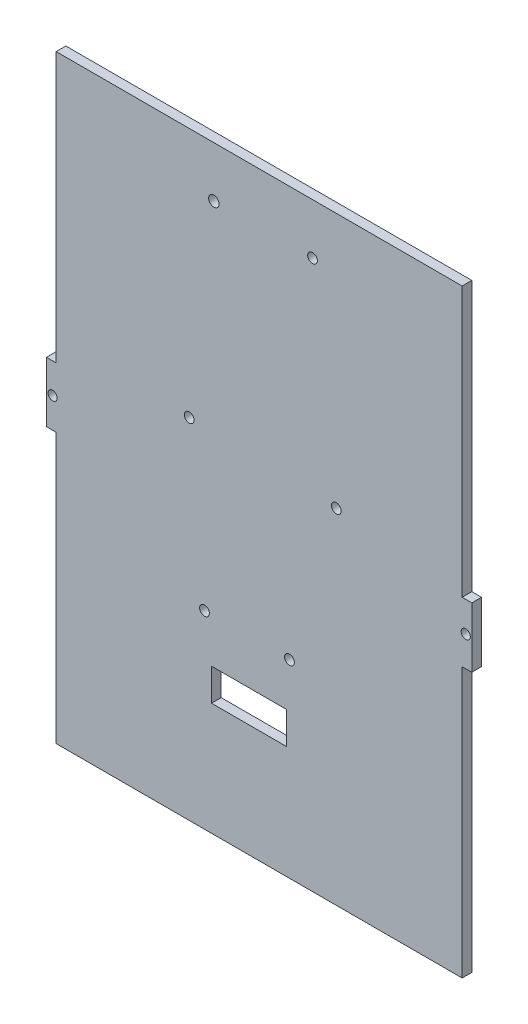
SolidWorks part; units mm, degrees
ref_plane "Front Plane" through (0, 0, 0) normal (0, 0, 1) x (1, 0, 0)
ref_plane "Top Plane" through (0, 0, 0) normal (0, 1, 0) x (1, 0, 0)
ref_plane "Right Plane" through (0, 0, 0) normal (1, 0, 0) x (0, 0, -1)
sketch "Sketch1" plane through (0, 0, 0) normal (0, 0, 1) x (1, 0, 0)
  line L1 (-69.85, 101.6) -> (69.85, 101.6)
  line L2 (-69.85, 101.6) -> (-69.85, -101.6)
  line L3 (-69.85, -101.6) -> (69.85, -101.6)
  line L4 (69.85, 101.6) -> (69.85, -101.6)
  line L5 (-69.85, 101.6) -> (69.85, -101.6) construction
  line L6 (-69.85, -101.6) -> (69.85, 101.6) construction
  point P0 (0, 0)
  dimension "D1" = 203.2
  dimension "D2" = 139.7
extrude "Boss-Extrude1" add sketch "Sketch1" along normal blind 3.18
sketch "Sketch2" plane through (0, 0, 3.18) normal (0, 0, 1) x (1, 0, 0)
  line L0 (0, 0) -> (69.85, 0) construction
  line L1 (-10, 101.6) -> (10, 101.6)
  line L2 (-10, 101.6) -> (-10, 98.42)
  line L3 (-10, 98.42) -> (-1.5, 98.42)
  line L4 (10, 101.6) -> (10, 98.42)
  line L5 (69.85, -101.6) -> (69.85, 101.6) construction
  line L6 (0, 0) -> (0, 101.6) construction
  line L7 (-1.5, 88.42) -> (1.5, 88.42)
  line L8 (-1.5, 88.42) -> (-1.5, 91.42)
  line L10 (1.5, 88.42) -> (1.5, 91.42)
  line L12 (69.85, 101.6) -> (-69.85, 101.6) construction
  line L13 (3.5, 94.42) -> (1.5, 94.42)
  line L14 (3.5, 94.42) -> (3.5, 91.42)
  line L15 (3.5, 91.42) -> (1.5, 91.42)
  line L16 (-3.5, 94.42) -> (-3.5, 91.42)
  line L17 (-10, -101.6) -> (-10, -98.42)
  line L18 (-10, -98.42) -> (-1.5, -98.42)
  line L19 (-1.5, -94.42) -> (-1.5, -98.42)
  line L20 (-1.5, -94.42) -> (-3.5, -94.42)
  line L21 (-3.5, -94.42) -> (-3.5, -91.42)
  line L22 (1.5, 98.42) -> (10, 98.42)
  line L23 (-1.5, 94.42) -> (-3.5, 94.42)
  line L24 (-1.5, -91.42) -> (-3.5, -91.42)
  line L25 (-1.5, -88.42) -> (-1.5, -91.42)
  line L26 (-1.5, -88.42) -> (1.5, -88.42)
  line L27 (-1.5, 91.42) -> (-3.5, 91.42)
  line L28 (1.5, -88.42) -> (1.5, -91.42)
  line L29 (-1.5, 94.42) -> (-1.5, 98.42)
  line L30 (1.5, 94.42) -> (1.5, 98.42)
  line L31 (3.5, -91.42) -> (1.5, -91.42)
  line L32 (3.5, -94.42) -> (3.5, -91.42)
  line L33 (3.5, -94.42) -> (1.5, -94.42)
  line L34 (1.5, -94.42) -> (1.5, -98.42)
  line L35 (1.5, -98.42) -> (10, -98.42)
  line L36 (10, -101.6) -> (10, -98.42)
  line L37 (-10, -101.6) -> (10, -101.6)
  line L38 (-69.85, 101.6) -> (-69.85, -101.6) construction
  line L39 (-69.85, 101.6) -> (-66.67, 101.6)
  line L40 (-69.85, 101.6) -> (-69.85, 9.875)
  line L41 (-69.85, 9.875) -> (-66.67, 9.875)
  line L42 (-66.67, 101.6) -> (-66.67, 9.875)
  line L43 (-69.85, -101.6) -> (-66.67, -101.6)
  line L44 (-69.85, -101.6) -> (-69.85, -9.875)
  line L45 (-69.85, -9.875) -> (-66.67, -9.875)
  line L46 (-66.67, -101.6) -> (-66.67, -9.875)
  line L47 (69.85, -9.875) -> (66.67, -9.875)
  line L48 (66.67, -101.6) -> (66.67, -9.875)
  line L49 (69.85, -101.6) -> (66.67, -101.6)
  line L50 (69.85, -101.6) -> (69.85, -9.875)
  line L51 (69.85, 9.875) -> (66.67, 9.875)
  line L52 (66.67, 101.6) -> (66.67, 9.875)
  line L53 (69.85, 101.6) -> (66.67, 101.6)
  line L54 (69.85, 101.6) -> (69.85, 9.875)
  circle A0 centre (-67.85, 0) radius 1.5
  circle A1 centre (67.85, 0) radius 1.5
  point P0 (0, 50.5662)
  point P5 (0, 32.0079)
  point P10 (15.4931, 34.4893)
  dimension "D11" = 3
  dimension "D12" = 2
  dimension "D1" = 20
  dimension "D2" = 19.75
  dimension "D3" = 4
  dimension "D4" = 3
  dimension "D5" = 3.18
  dimension "D6" = 7
  dimension "D7" = 3
  dimension "D8" = 3
  dimension "D9" = 3.18
  dimension "D10" = 3.18
extrude "Cut-Extrude1" cut sketch "Sketch2" against normal through all
sketch "Sketch3" plane through (0, 0, 0) normal (0, 0, -1) x (-1, 0, 0)
  circle A0 centre (-35.6713, -47.9634) radius 1.59
  circle A1 centre (-35.6713, -30.7773) radius 1.59
extrude "Cut-Extrude2" cut sketch "Sketch3" against normal through all
sketch "Sketch4" plane through (0, 0, 0) normal (0, 0, -1) x (-1, 0, 0)
  circle A0 centre (-34.7507, 80.7361) radius 1.59
  circle A1 centre (-34.7507, 63.55) radius 1.59
  circle A2 centre (36.2498, 80.7361) radius 1.59
  circle A3 centre (36.2498, 63.55) radius 1.59
  circle A4 centre (35.9839, -30.7773) radius 1.59
  circle A5 centre (35.9839, -47.9634) radius 1.59
  circle A6 centre (-35.6713, -30.7773) radius 1.59
  circle A7 centre (-35.6713, -47.9634) radius 1.59
extrude "Cut-Extrude3" cut sketch "Sketch4" against normal through all
sketch "Sketch5" plane through (0, 0, 3.18) normal (0, 0, 1) x (1, 0, 0)
  line L1 (-44.4479, 84.2814) -> (44.4479, 84.2814)
  line L2 (-44.4479, 84.2814) -> (-44.4479, -84.2814)
  line L3 (-44.4479, -84.2814) -> (44.4479, -84.2814)
  line L4 (44.4479, 84.2814) -> (44.4479, -84.2814)
  line L5 (-44.4479, 84.2814) -> (44.4479, -84.2814) construction
  line L6 (-44.4479, -84.2814) -> (44.4479, 84.2814) construction
  point P0 (0, 0)
extrude "Boss-Extrude2" add sketch "Sketch5" against normal blind 3.18
sketch "Sketch6" plane through (0, 0, 3.18) normal (0, 0, 1) x (1, 0, 0)
  line L1 (-10, 101.6) -> (10, 101.6)
  line L2 (-10, 101.6) -> (-10, -101.6)
  line L3 (-10, -101.6) -> (10, -101.6)
  line L4 (10, 101.6) -> (10, -101.6)
extrude "Boss-Extrude3" add sketch "Sketch6" against normal blind 3.18
sketch "Sketch7" plane through (0, 0, 3.18) normal (0, 0, 1) x (1, 0, 0)
  line L0 (0, 0) -> (0, -20.0062) construction
  line L1 (-66.67, -101.6) -> (-9.875, -101.6)
  line L2 (-66.67, -101.6) -> (-66.67, -98.42)
  line L3 (-66.67, -98.42) -> (-9.875, -98.42)
  line L4 (-9.875, -101.6) -> (-9.875, -98.42)
  line L5 (66.67, -101.6) -> (9.875, -101.6)
  line L6 (66.67, -101.6) -> (66.67, -98.42)
  line L7 (66.67, -98.42) -> (9.875, -98.42)
  line L8 (9.875, -101.6) -> (9.875, -98.42)
  dimension "D1" = 3.18
  dimension "D2" = 3.18
  dimension "D3" = 19.75
extrude "Cut-Extrude4" cut sketch "Sketch7" against normal through all
sketch "Sketch8" plane through (0, 0, 3.18) normal (0, 0, 1) x (1, 0, 0)
  line L0 (-66.67, 9.875) -> (-66.67, 101.6) construction
  line L1 (66.67, 101.6) -> (-66.67, 101.6)
  line L2 (66.67, 101.6) -> (66.67, 98.42)
  line L3 (66.67, 98.42) -> (-66.67, 98.42)
  line L4 (-66.67, 101.6) -> (-66.67, 98.42)
  line L5 (-9.875, 98.42) -> (-69.85, 98.42) construction
extrude "Cut-Extrude5" cut sketch "Sketch8" against normal through all
sketch "Sketch9" plane through (0, 0, 3.18) normal (0, 0, 1) x (1, 0, 0)
  circle A0 centre (-17.9479, -36.2051) radius 1.6
  circle A1 centre (25.3331, 14.5259) radius 1.6
  circle A2 centre (-22.9643, 16.203) radius 1.6
  circle A3 centre (9.952, -36.2496) radius 1.6
extrude "Cut-Extrude6" cut sketch "Sketch9" against normal through all
sketch "Sketch10" plane through (0, 0, 3.18) normal (0, 0, 1) x (1, 0, 0)
  line L1 (8.9231, -61.4181) -> (-15.6427, -61.4181)
  line L2 (8.9231, -61.4181) -> (8.9231, -50.8809)
  line L3 (8.9231, -50.8809) -> (-15.6427, -50.8809)
  line L4 (-15.6427, -61.4181) -> (-15.6427, -50.8809)
extrude "Cut-Extrude7" cut sketch "Sketch10" against normal blind 3.18
sketch "Sketch11" plane through (0, 0, 3.18) normal (0, 0, 1) x (1, 0, 0)
  circle A0 centre (17.5239, 81.7974) radius 1.59
  circle A1 centre (-14.8831, 81.7974) radius 1.7179
extrude "Cut-Extrude8" cut sketch "Sketch11" against normal blind 35
sketch "Sketch12" plane through (-9.875, 0, 0) normal (-1, 0, 0) x (0, 0, 1)
  line L1 (3.18, -98.42) -> (0, -98.42)
  line L2 (3.18, -98.42) -> (3.18, -101.6)
  line L3 (3.18, -101.6) -> (0, -101.6)
  line L4 (0, -98.42) -> (0, -101.6)
extrude "Cut-Extrude9" cut sketch "Sketch12" against normal through all
